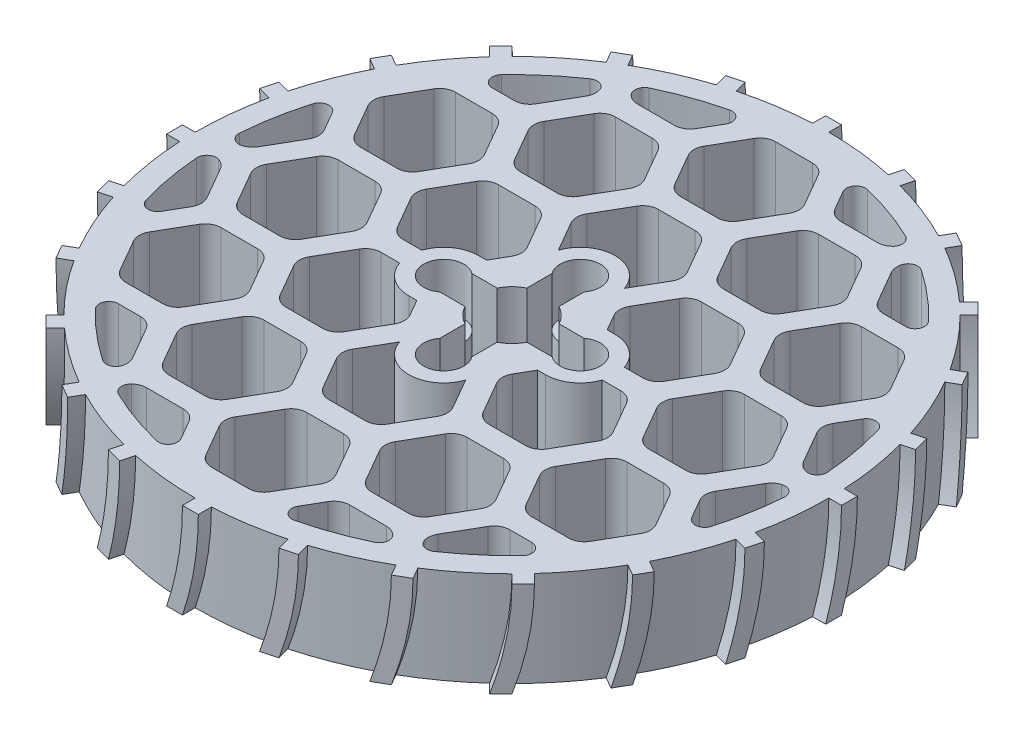
SolidWorks part; units mm, degrees
ref_plane "Front Plane" through (0, 0, 0) normal (0, 0, 1) x (1, 0, 0)
ref_plane "Top Plane" through (0, 0, 0) normal (0, 1, 0) x (1, 0, 0)
ref_plane "Right Plane" through (0, 0, 0) normal (1, 0, 0) x (0, 0, -1)
sketch "Sketch2" plane through (0, 0, 0) normal (0, 1, 0) x (1, 0, 0)
  line L0 (-17.7275, -5.0583) -> (-9.768, -5.0583)
  line L1 (-17.7275, 5.0583) -> (-9.768, 5.0583)
  line L2 (-21.548, 11) -> (-11, 11)
  line L3 (-21.548, -11) -> (-11, -11)
  line L4 (-21.548, 0) -> (0, 0) construction
  line L5 (11, 21.548) -> (11, 11)
  line L6 (-11, 21.548) -> (-11, 11)
  line L7 (5.0583, 17.7275) -> (5.0583, 9.768)
  line L8 (-5.0583, 17.7275) -> (-5.0583, 9.768)
  line L9 (21.548, -11) -> (11, -11)
  line L10 (21.548, 11) -> (11, 11)
  line L11 (17.7275, -5.0583) -> (9.768, -5.0583)
  line L12 (17.7275, 5.0583) -> (9.768, 5.0583)
  line L13 (-11, -21.548) -> (-11, -11)
  line L14 (11, -21.548) -> (11, -11)
  line L15 (-5.0583, -17.7275) -> (-5.0583, -9.768)
  line L16 (5.0583, -17.7275) -> (5.0583, -9.768)
  line L17 (0, 0) -> (-12.9904, 7.5) construction
  line L18 (-15.8771, -2.5) -> (-10.1036, -12.5)
  line L19 (-5.7735, -15) -> (5.7735, -15)
  line L20 (10.1036, -12.5) -> (15.8771, -2.5)
  line L21 (15.8771, 2.5) -> (10.1036, 12.5)
  line L22 (5.7735, 15) -> (-5.7735, 15)
  line L23 (-10.1036, 12.5) -> (-15.8771, 2.5)
  arc A0 (-21.548, 11) -> (-21.548, -11) centre (-21.548, 0) ccw
  arc A1 (-5.0583, 9.768) -> (-9.768, 5.0583) centre (0, 0) ccw
  circle A2 centre (-21.548, 0) radius 3.302
  circle A3 centre (-21.548, 0) radius 6.339
  arc A4 (-5.0583, 9.768) -> (-9.768, 5.0583) centre (0, 0) ccw
  arc A5 (11, 21.548) -> (-11, 21.548) centre (0, 21.548) ccw
  circle A6 centre (0, 21.548) radius 6.339
  circle A7 centre (0, 21.548) radius 3.302
  arc A8 (21.548, -11) -> (21.548, 11) centre (21.548, 0) ccw
  circle A9 centre (21.548, 0) radius 6.339
  circle A10 centre (21.548, 0) radius 3.302
  arc A11 (-11, -21.548) -> (11, -21.548) centre (0, -21.548) ccw
  circle A12 centre (0, -21.548) radius 6.339
  circle A13 centre (0, -21.548) radius 3.302
  arc A14 (9.768, 5.0583) -> (5.0583, 9.768) centre (0, 0) ccw
  arc A15 (5.0583, -9.768) -> (9.768, -5.0583) centre (0, 0) ccw
  arc A16 (-9.768, -5.0583) -> (-5.0583, -9.768) centre (0, 0) ccw
  circle A17 centre (0, 0) radius 100
  circle A18 centre (0, 0) radius 15 construction
  arc A19 (10.1036, 12.5) -> (5.7735, 15) centre (5.7735, 10) ccw
  arc A20 (15.8771, -2.5) -> (15.8771, 2.5) centre (11.547, 0) ccw
  arc A21 (10.1036, -12.5) -> (5.7735, -15) centre (5.7735, -10) cw
  arc A22 (-10.1036, -12.5) -> (-5.7735, -15) centre (-5.7735, -10) ccw
  arc A23 (-15.8771, -2.5) -> (-15.8771, 2.5) centre (-11.547, 0) cw
  arc A24 (-10.1036, 12.5) -> (-5.7735, 15) centre (-5.7735, 10) cw
  point P59 (0, 0)
  dimension "D1" = 6.604
  dimension "D2" = 12.678
  dimension "D3" = 11
  dimension "D8" = 22
  dimension "D10" = 200
  dimension "D12" = 5
  dimension "D4" = 21.548
  dimension "D5" = 7.9595
  dimension "D6" = 10.548
  dimension "D7" = 10.548
  dimension "D11" = 30
  dimension "D13" = 30
  dimension "D9" = 4
sketch "Sketch3" plane through (0, 0, 0) normal (0, 1, 0) x (1, 0, 0)
  line L0 (0, 0) -> (16.547, 0) construction
  line L1 (5.7735, 15) -> (-5.7735, 15)
  line L2 (-10.1036, 12.5) -> (-15.8771, 2.5)
  line L3 (-15.8771, -2.5) -> (-10.1036, -12.5)
  line L4 (-5.7735, -15) -> (5.7735, -15)
  line L5 (10.1036, -12.5) -> (15.8771, -2.5)
  line L6 (15.8771, 2.5) -> (10.1036, 12.5)
  line L7 (37.8164, 33.5) -> (26.2694, 33.5)
  line L8 (21.9393, 31) -> (16.1658, 21)
  line L9 (16.1658, 16) -> (21.9393, 6)
  line L10 (26.2694, 3.5) -> (37.8164, 3.5)
  line L11 (42.1466, 6) -> (47.9201, 16)
  line L12 (47.9201, 21) -> (42.1466, 31)
  line L13 (69.8594, 52) -> (58.3124, 52)
  line L14 (53.9823, 49.5) -> (48.2087, 39.5)
  line L15 (48.2087, 34.5) -> (53.9823, 24.5)
  line L16 (58.3124, 22) -> (69.8594, 22)
  line L17 (74.1895, 24.5) -> (79.963, 34.5)
  line L18 (79.963, 39.5) -> (74.1895, 49.5)
  line L19 (101.9023, 70.5) -> (90.3553, 70.5)
  line L20 (86.0252, 68) -> (80.2517, 58)
  line L21 (80.2517, 53) -> (86.0252, 43)
  line L22 (90.3553, 40.5) -> (101.9023, 40.5)
  line L23 (106.2324, 43) -> (112.006, 53)
  line L24 (112.006, 58) -> (106.2324, 68)
  line L25 (37.8164, 70.5) -> (26.2694, 70.5)
  line L26 (21.9393, 68) -> (16.1658, 58)
  line L27 (16.1658, 53) -> (21.9393, 43)
  line L28 (26.2694, 40.5) -> (37.8164, 40.5)
  line L29 (42.1466, 43) -> (47.9201, 53)
  line L30 (47.9201, 58) -> (42.1466, 68)
  line L31 (69.8594, 89) -> (58.3124, 89)
  line L32 (53.9823, 86.5) -> (48.2087, 76.5)
  line L33 (48.2087, 71.5) -> (53.9823, 61.5)
  line L34 (58.3124, 59) -> (69.8594, 59)
  line L35 (74.1895, 61.5) -> (79.963, 71.5)
  line L36 (79.963, 76.5) -> (74.1895, 86.5)
  line L37 (101.9023, 107.5) -> (90.3553, 107.5) [skipped]
  line L38 (86.0252, 105) -> (80.2517, 95) [skipped]
  line L39 (80.2517, 90) -> (86.0252, 80) [skipped]
  line L40 (90.3553, 77.5) -> (101.9023, 77.5) [skipped]
  line L41 (106.2324, 80) -> (112.006, 90) [skipped]
  line L42 (112.006, 95) -> (106.2324, 105) [skipped]
  line L43 (37.8164, 107.5) -> (26.2694, 107.5)
  line L44 (21.9393, 105) -> (16.1658, 95)
  line L45 (16.1658, 90) -> (21.9393, 80)
  line L46 (26.2694, 77.5) -> (37.8164, 77.5)
  line L47 (42.1466, 80) -> (47.9201, 90)
  line L48 (47.9201, 95) -> (42.1466, 105)
  line L49 (69.8594, 126) -> (58.3124, 126) [skipped]
  line L50 (53.9823, 123.5) -> (48.2087, 113.5) [skipped]
  line L51 (48.2087, 108.5) -> (53.9823, 98.5) [skipped]
  line L52 (58.3124, 96) -> (69.8594, 96) [skipped]
  line L53 (74.1895, 98.5) -> (79.963, 108.5) [skipped]
  line L54 (79.963, 113.5) -> (74.1895, 123.5) [skipped]
  line L55 (101.9023, 144.5) -> (90.3553, 144.5) [skipped]
  line L56 (86.0252, 142) -> (80.2517, 132) [skipped]
  line L57 (80.2517, 127) -> (86.0252, 117) [skipped]
  line L58 (90.3553, 114.5) -> (101.9023, 114.5) [skipped]
  line L59 (106.2324, 117) -> (112.006, 127) [skipped]
  line L60 (112.006, 132) -> (106.2324, 142) [skipped]
  line L61 (37.8164, 144.5) -> (26.2694, 144.5) [skipped]
  line L62 (21.9393, 142) -> (16.1658, 132) [skipped]
  line L63 (16.1658, 127) -> (21.9393, 117) [skipped]
  line L64 (26.2694, 114.5) -> (37.8164, 114.5) [skipped]
  line L65 (42.1466, 117) -> (47.9201, 127) [skipped]
  line L66 (47.9201, 132) -> (42.1466, 142) [skipped]
  line L67 (69.8594, 163) -> (58.3124, 163) [skipped]
  line L68 (53.9823, 160.5) -> (48.2087, 150.5) [skipped]
  line L69 (48.2087, 145.5) -> (53.9823, 135.5) [skipped]
  line L70 (58.3124, 133) -> (69.8594, 133) [skipped]
  line L71 (74.1895, 135.5) -> (79.963, 145.5) [skipped]
  line L72 (79.963, 150.5) -> (74.1895, 160.5) [skipped]
  line L73 (101.9023, 181.5) -> (90.3553, 181.5) [skipped]
  line L74 (86.0252, 179) -> (80.2517, 169) [skipped]
  line L75 (80.2517, 164) -> (86.0252, 154) [skipped]
  line L76 (90.3553, 151.5) -> (101.9023, 151.5) [skipped]
  line L77 (106.2324, 154) -> (112.006, 164) [skipped]
  line L78 (112.006, 169) -> (106.2324, 179) [skipped]
  line L79 (5.7735, 52) -> (-5.7735, 52) [skipped]
  line L80 (-10.1036, 49.5) -> (-15.8771, 39.5) [skipped]
  line L81 (-15.8771, 34.5) -> (-10.1036, 24.5) [skipped]
  line L82 (-5.7735, 22) -> (5.7735, 22) [skipped]
  line L83 (10.1036, 24.5) -> (15.8771, 34.5) [skipped]
  line L84 (15.8771, 39.5) -> (10.1036, 49.5) [skipped]
  line L85 (5.7735, 89) -> (-5.7735, 89) [skipped]
  line L86 (-10.1036, 86.5) -> (-15.8771, 76.5) [skipped]
  line L87 (-15.8771, 71.5) -> (-10.1036, 61.5) [skipped]
  line L88 (-5.7735, 59) -> (5.7735, 59) [skipped]
  line L89 (10.1036, 61.5) -> (15.8771, 71.5) [skipped]
  line L90 (15.8771, 76.5) -> (10.1036, 86.5) [skipped]
  line L91 (5.7735, 126) -> (-5.7735, 126) [skipped]
  line L92 (-10.1036, 123.5) -> (-15.8771, 113.5) [skipped]
  line L93 (-15.8771, 108.5) -> (-10.1036, 98.5) [skipped]
  line L94 (-5.7735, 96) -> (5.7735, 96) [skipped]
  line L95 (10.1036, 98.5) -> (15.8771, 108.5) [skipped]
  line L96 (15.8771, 113.5) -> (10.1036, 123.5) [skipped]
  line L97 (0, 0) -> (83.1384, 48) construction
  line L98 (112.006, 21) -> (106.2324, 31)
  line L99 (101.9023, 33.5) -> (90.3553, 33.5)
  line L100 (86.0252, 31) -> (80.2517, 21)
  line L101 (80.2517, 16) -> (86.0252, 6)
  line L102 (90.3553, 3.5) -> (101.9023, 3.5)
  line L103 (106.2324, 6) -> (112.006, 16)
  line L104 (112.006, -16) -> (106.2324, -6)
  line L105 (101.9023, -3.5) -> (90.3553, -3.5)
  line L106 (86.0252, -6) -> (80.2517, -16)
  line L107 (80.2517, -21) -> (86.0252, -31)
  line L108 (90.3553, -33.5) -> (101.9023, -33.5)
  line L109 (106.2324, -31) -> (112.006, -21)
  line L110 (112.006, -53) -> (106.2324, -43)
  line L111 (101.9023, -40.5) -> (90.3553, -40.5)
  line L112 (86.0252, -43) -> (80.2517, -53)
  line L113 (80.2517, -58) -> (86.0252, -68)
  line L114 (90.3553, -70.5) -> (101.9023, -70.5)
  line L115 (106.2324, -68) -> (112.006, -58)
  line L116 (79.963, -34.5) -> (74.1895, -24.5)
  line L117 (69.8594, -22) -> (58.3124, -22)
  line L118 (53.9823, -24.5) -> (48.2087, -34.5)
  line L119 (48.2087, -39.5) -> (53.9823, -49.5)
  line L120 (58.3124, -52) -> (69.8594, -52)
  line L121 (74.1895, -49.5) -> (79.963, -39.5)
  line L122 (79.963, 2.5) -> (74.1895, 12.5)
  line L123 (69.8594, 15) -> (58.3124, 15)
  line L124 (53.9823, 12.5) -> (48.2087, 2.5)
  line L125 (48.2087, -2.5) -> (53.9823, -12.5)
  line L126 (58.3124, -15) -> (69.8594, -15)
  line L127 (74.1895, -12.5) -> (79.963, -2.5)
  line L128 (47.9201, -16) -> (42.1466, -6)
  line L129 (37.8164, -3.5) -> (26.2694, -3.5)
  line L130 (21.9393, -6) -> (16.1658, -16)
  line L131 (16.1658, -21) -> (21.9393, -31)
  line L132 (26.2694, -33.5) -> (37.8164, -33.5)
  line L133 (42.1466, -31) -> (47.9201, -21)
  line L134 (74.1895, -86.5) -> (79.963, -76.5)
  line L135 (79.963, -71.5) -> (74.1895, -61.5)
  line L136 (69.8594, -59) -> (58.3124, -59)
  line L137 (53.9823, -61.5) -> (48.2087, -71.5)
  line L138 (48.2087, -76.5) -> (53.9823, -86.5)
  line L139 (58.3124, -89) -> (69.8594, -89)
  line L140 (42.1466, -105) -> (47.9201, -95)
  line L141 (47.9201, -90) -> (42.1466, -80)
  line L142 (37.8164, -77.5) -> (26.2694, -77.5)
  line L143 (21.9393, -80) -> (16.1658, -90)
  line L144 (16.1658, -95) -> (21.9393, -105)
  line L145 (26.2694, -107.5) -> (37.8164, -107.5)
  line L146 (10.1036, -123.5) -> (15.8771, -113.5)
  line L147 (15.8771, -108.5) -> (10.1036, -98.5)
  line L148 (5.7735, -96) -> (-5.7735, -96)
  line L149 (-10.1036, -98.5) -> (-15.8771, -108.5)
  line L150 (-15.8771, -113.5) -> (-10.1036, -123.5)
  line L151 (-5.7735, -126) -> (5.7735, -126)
  line L152 (10.1036, -86.5) -> (15.8771, -76.5)
  line L153 (15.8771, -71.5) -> (10.1036, -61.5)
  line L154 (5.7735, -59) -> (-5.7735, -59)
  line L155 (-10.1036, -61.5) -> (-15.8771, -71.5)
  line L156 (-15.8771, -76.5) -> (-10.1036, -86.5)
  line L157 (-5.7735, -89) -> (5.7735, -89)
  line L158 (42.1466, -68) -> (47.9201, -58)
  line L159 (47.9201, -53) -> (42.1466, -43)
  line L160 (37.8164, -40.5) -> (26.2694, -40.5)
  line L161 (21.9393, -43) -> (16.1658, -53)
  line L162 (16.1658, -58) -> (21.9393, -68)
  line L163 (26.2694, -70.5) -> (37.8164, -70.5)
  line L164 (10.1036, -49.5) -> (15.8771, -39.5)
  line L165 (15.8771, -34.5) -> (10.1036, -24.5)
  line L166 (5.7735, -22) -> (-5.7735, -22)
  line L167 (-10.1036, -24.5) -> (-15.8771, -34.5)
  line L168 (-15.8771, -39.5) -> (-10.1036, -49.5)
  line L169 (-5.7735, -52) -> (5.7735, -52)
  line L170 (-37.8164, -107.5) -> (-26.2694, -107.5)
  line L171 (-21.9393, -105) -> (-16.1658, -95)
  line L172 (-16.1658, -90) -> (-21.9393, -80)
  line L173 (-26.2694, -77.5) -> (-37.8164, -77.5)
  line L174 (-42.1466, -80) -> (-47.9201, -90)
  line L175 (-47.9201, -95) -> (-42.1466, -105)
  line L176 (-69.8594, -89) -> (-58.3124, -89)
  line L177 (-53.9823, -86.5) -> (-48.2087, -76.5)
  line L178 (-48.2087, -71.5) -> (-53.9823, -61.5)
  line L179 (-58.3124, -59) -> (-69.8594, -59)
  line L180 (-74.1895, -61.5) -> (-79.963, -71.5)
  line L181 (-79.963, -76.5) -> (-74.1895, -86.5)
  line L182 (-101.9023, -70.5) -> (-90.3553, -70.5)
  line L183 (-86.0252, -68) -> (-80.2517, -58)
  line L184 (-80.2517, -53) -> (-86.0252, -43)
  line L185 (-90.3553, -40.5) -> (-101.9023, -40.5)
  line L186 (-106.2324, -43) -> (-112.006, -53)
  line L187 (-112.006, -58) -> (-106.2324, -68)
  line L188 (-69.8594, -52) -> (-58.3124, -52)
  line L189 (-53.9823, -49.5) -> (-48.2087, -39.5)
  line L190 (-48.2087, -34.5) -> (-53.9823, -24.5)
  line L191 (-58.3124, -22) -> (-69.8594, -22)
  line L192 (-74.1895, -24.5) -> (-79.963, -34.5)
  line L193 (-79.963, -39.5) -> (-74.1895, -49.5)
  line L194 (-37.8164, -70.5) -> (-26.2694, -70.5)
  line L195 (-21.9393, -68) -> (-16.1658, -58)
  line L196 (-16.1658, -53) -> (-21.9393, -43)
  line L197 (-26.2694, -40.5) -> (-37.8164, -40.5)
  line L198 (-42.1466, -43) -> (-47.9201, -53)
  line L199 (-47.9201, -58) -> (-42.1466, -68)
  line L200 (-37.8164, -33.5) -> (-26.2694, -33.5)
  line L201 (-21.9393, -31) -> (-16.1658, -21)
  line L202 (-16.1658, -16) -> (-21.9393, -6)
  line L203 (-26.2694, -3.5) -> (-37.8164, -3.5)
  line L204 (-42.1466, -6) -> (-47.9201, -16)
  line L205 (-47.9201, -21) -> (-42.1466, -31)
  line L206 (-112.006, -21) -> (-106.2324, -31)
  line L207 (-101.9023, -33.5) -> (-90.3553, -33.5)
  line L208 (-86.0252, -31) -> (-80.2517, -21)
  line L209 (-80.2517, -16) -> (-86.0252, -6)
  line L210 (-90.3553, -3.5) -> (-101.9023, -3.5)
  line L211 (-106.2324, -6) -> (-112.006, -16)
  line L212 (-112.006, 16) -> (-106.2324, 6)
  line L213 (-101.9023, 3.5) -> (-90.3553, 3.5)
  line L214 (-86.0252, 6) -> (-80.2517, 16)
  line L215 (-80.2517, 21) -> (-86.0252, 31)
  line L216 (-90.3553, 33.5) -> (-101.9023, 33.5)
  line L217 (-106.2324, 31) -> (-112.006, 21)
  line L218 (-112.006, 53) -> (-106.2324, 43)
  line L219 (-101.9023, 40.5) -> (-90.3553, 40.5)
  line L220 (-86.0252, 43) -> (-80.2517, 53)
  line L221 (-80.2517, 58) -> (-86.0252, 68)
  line L222 (-90.3553, 70.5) -> (-101.9023, 70.5)
  line L223 (-106.2324, 68) -> (-112.006, 58)
  line L224 (-79.963, 34.5) -> (-74.1895, 24.5)
  line L225 (-69.8594, 22) -> (-58.3124, 22)
  line L226 (-53.9823, 24.5) -> (-48.2087, 34.5)
  line L227 (-48.2087, 39.5) -> (-53.9823, 49.5)
  line L228 (-58.3124, 52) -> (-69.8594, 52)
  line L229 (-74.1895, 49.5) -> (-79.963, 39.5)
  line L230 (-79.963, -2.5) -> (-74.1895, -12.5)
  line L231 (-69.8594, -15) -> (-58.3124, -15)
  line L232 (-53.9823, -12.5) -> (-48.2087, -2.5)
  line L233 (-48.2087, 2.5) -> (-53.9823, 12.5)
  line L234 (-58.3124, 15) -> (-69.8594, 15)
  line L235 (-74.1895, 12.5) -> (-79.963, 2.5)
  line L236 (-47.9201, 16) -> (-42.1466, 6)
  line L237 (-37.8164, 3.5) -> (-26.2694, 3.5)
  line L238 (-21.9393, 6) -> (-16.1658, 16)
  line L239 (-16.1658, 21) -> (-21.9393, 31)
  line L240 (-26.2694, 33.5) -> (-37.8164, 33.5)
  line L241 (-42.1466, 31) -> (-47.9201, 21)
  line L242 (-74.1895, 86.5) -> (-79.963, 76.5)
  line L243 (-79.963, 71.5) -> (-74.1895, 61.5)
  line L244 (-69.8594, 59) -> (-58.3124, 59)
  line L245 (-53.9823, 61.5) -> (-48.2087, 71.5)
  line L246 (-48.2087, 76.5) -> (-53.9823, 86.5)
  line L247 (-58.3124, 89) -> (-69.8594, 89)
  line L248 (-42.1466, 105) -> (-47.9201, 95)
  line L249 (-47.9201, 90) -> (-42.1466, 80)
  line L250 (-37.8164, 77.5) -> (-26.2694, 77.5)
  line L251 (-21.9393, 80) -> (-16.1658, 90)
  line L252 (-16.1658, 95) -> (-21.9393, 105)
  line L253 (-26.2694, 107.5) -> (-37.8164, 107.5)
  line L254 (-10.1036, 123.5) -> (-15.8771, 113.5)
  line L255 (-15.8771, 108.5) -> (-10.1036, 98.5)
  line L256 (-5.7735, 96) -> (5.7735, 96)
  line L257 (10.1036, 98.5) -> (15.8771, 108.5)
  line L258 (15.8771, 113.5) -> (10.1036, 123.5)
  line L259 (5.7735, 126) -> (-5.7735, 126)
  line L260 (-10.1036, 86.5) -> (-15.8771, 76.5)
  line L261 (-15.8771, 71.5) -> (-10.1036, 61.5)
  line L262 (-5.7735, 59) -> (5.7735, 59)
  line L263 (10.1036, 61.5) -> (15.8771, 71.5)
  line L264 (15.8771, 76.5) -> (10.1036, 86.5)
  line L265 (5.7735, 89) -> (-5.7735, 89)
  line L266 (-42.1466, 68) -> (-47.9201, 58)
  line L267 (-47.9201, 53) -> (-42.1466, 43)
  line L268 (-37.8164, 40.5) -> (-26.2694, 40.5)
  line L269 (-21.9393, 43) -> (-16.1658, 53)
  line L270 (-16.1658, 58) -> (-21.9393, 68)
  line L271 (-26.2694, 70.5) -> (-37.8164, 70.5)
  line L272 (-10.1036, 49.5) -> (-15.8771, 39.5)
  line L273 (-15.8771, 34.5) -> (-10.1036, 24.5)
  line L274 (-5.7735, 22) -> (5.7735, 22)
  line L275 (10.1036, 24.5) -> (15.8771, 34.5)
  line L276 (15.8771, 39.5) -> (10.1036, 49.5)
  line L277 (5.7735, 52) -> (-5.7735, 52)
  line L278 (0, 0) -> (0, 96) construction
  line L279 (0, 0) -> (-83.1384, 48) construction
  line L280 (-17.7275, -5.0583) -> (-9.768, -5.0583)
  line L281 (-17.7275, 5.0583) -> (-9.768, 5.0583)
  line L282 (-21.548, 11) -> (-11, 11)
  line L283 (-21.548, -11) -> (-11, -11)
  line L284 (0, 0) -> (-21.548, 0) construction
  line L285 (11, 21.548) -> (11, 11)
  line L286 (-11, 21.548) -> (-11, 11)
  line L287 (-5.0583, 17.7275) -> (-5.0583, 9.768)
  line L288 (5.0583, 17.7275) -> (5.0583, 9.768)
  line L289 (21.548, -11) -> (11, -11)
  line L290 (21.548, 11) -> (11, 11)
  line L291 (17.7275, 5.0583) -> (9.768, 5.0583)
  line L292 (17.7275, -5.0583) -> (9.768, -5.0583)
  line L293 (-11, -21.548) -> (-11, -11)
  line L294 (11, -21.548) -> (11, -11)
  line L295 (5.0583, -17.7275) -> (5.0583, -9.768)
  line L296 (-5.0583, -17.7275) -> (-5.0583, -9.768)
  line L297 (0, 0) -> (0, 21.548) construction
  circle A0 centre (0, 0) radius 15 construction
  arc A1 (10.1036, 12.5) -> (5.7735, 15) centre (5.7735, 10) ccw
  arc A2 (15.8771, 2.5) -> (15.8771, -2.5) centre (11.547, 0) cw
  arc A3 (5.7735, -15) -> (10.1036, -12.5) centre (5.7735, -10) ccw
  arc A4 (-5.7735, -15) -> (-10.1036, -12.5) centre (-5.7735, -10) cw
  arc A5 (-15.8771, -2.5) -> (-15.8771, 2.5) centre (-11.547, 0) cw
  arc A6 (-10.1036, 12.5) -> (-5.7735, 15) centre (-5.7735, 10) cw
  circle A7 centre (0, 0) radius 100
  arc A8 (21.9393, 31) -> (26.2694, 33.5) centre (26.2694, 28.5) cw
  arc A9 (42.1466, 31) -> (37.8164, 33.5) centre (37.8164, 28.5) ccw
  arc A10 (16.1658, 16) -> (16.1658, 21) centre (20.4959, 18.5) cw
  arc A11 (26.2694, 3.5) -> (21.9393, 6) centre (26.2694, 8.5) cw
  arc A12 (37.8164, 3.5) -> (42.1466, 6) centre (37.8164, 8.5) ccw
  arc A13 (47.9201, 21) -> (47.9201, 16) centre (43.5899, 18.5) cw
  arc A14 (53.9823, 49.5) -> (58.3124, 52) centre (58.3124, 47) cw
  arc A15 (74.1895, 49.5) -> (69.8594, 52) centre (69.8594, 47) ccw
  arc A16 (48.2087, 34.5) -> (48.2087, 39.5) centre (52.5389, 37) cw
  arc A17 (58.3124, 22) -> (53.9823, 24.5) centre (58.3124, 27) cw
  arc A18 (69.8594, 22) -> (74.1895, 24.5) centre (69.8594, 27) ccw
  arc A19 (79.963, 39.5) -> (79.963, 34.5) centre (75.6329, 37) cw
  arc A20 (86.0252, 68) -> (90.3553, 70.5) centre (90.3553, 65.5) cw
  arc A21 (106.2324, 68) -> (101.9023, 70.5) centre (101.9023, 65.5) ccw
  arc A22 (80.2517, 53) -> (80.2517, 58) centre (84.5818, 55.5) cw
  arc A23 (90.3553, 40.5) -> (86.0252, 43) centre (90.3553, 45.5) cw
  arc A24 (101.9023, 40.5) -> (106.2324, 43) centre (101.9023, 45.5) ccw
  arc A25 (112.006, 58) -> (112.006, 53) centre (107.6758, 55.5) cw
  arc A26 (21.9393, 68) -> (26.2694, 70.5) centre (26.2694, 65.5) cw
  arc A27 (42.1466, 68) -> (37.8164, 70.5) centre (37.8164, 65.5) ccw
  arc A28 (16.1658, 53) -> (16.1658, 58) centre (20.4959, 55.5) cw
  arc A29 (26.2694, 40.5) -> (21.9393, 43) centre (26.2694, 45.5) cw
  arc A30 (37.8164, 40.5) -> (42.1466, 43) centre (37.8164, 45.5) ccw
  arc A31 (47.9201, 58) -> (47.9201, 53) centre (43.5899, 55.5) cw
  arc A32 (53.9823, 86.5) -> (58.3124, 89) centre (58.3124, 84) cw
  arc A33 (74.1895, 86.5) -> (69.8594, 89) centre (69.8594, 84) ccw
  arc A34 (48.2087, 71.5) -> (48.2087, 76.5) centre (52.5389, 74) cw
  arc A35 (58.3124, 59) -> (53.9823, 61.5) centre (58.3124, 64) cw
  arc A36 (69.8594, 59) -> (74.1895, 61.5) centre (69.8594, 64) ccw
  arc A37 (79.963, 76.5) -> (79.963, 71.5) centre (75.6329, 74) cw
  arc A38 (86.0252, 105) -> (90.3553, 107.5) centre (90.3553, 102.5) cw [skipped]
  arc A39 (106.2324, 105) -> (101.9023, 107.5) centre (101.9023, 102.5) ccw [skipped]
  arc A40 (80.2517, 90) -> (80.2517, 95) centre (84.5818, 92.5) cw [skipped]
  arc A41 (90.3553, 77.5) -> (86.0252, 80) centre (90.3553, 82.5) cw [skipped]
  arc A42 (101.9023, 77.5) -> (106.2324, 80) centre (101.9023, 82.5) ccw [skipped]
  arc A43 (112.006, 95) -> (112.006, 90) centre (107.6758, 92.5) cw [skipped]
  arc A44 (21.9393, 105) -> (26.2694, 107.5) centre (26.2694, 102.5) cw
  arc A45 (42.1466, 105) -> (37.8164, 107.5) centre (37.8164, 102.5) ccw
  arc A46 (16.1658, 90) -> (16.1658, 95) centre (20.4959, 92.5) cw
  arc A47 (26.2694, 77.5) -> (21.9393, 80) centre (26.2694, 82.5) cw
  arc A48 (37.8164, 77.5) -> (42.1466, 80) centre (37.8164, 82.5) ccw
  arc A49 (47.9201, 95) -> (47.9201, 90) centre (43.5899, 92.5) cw
  arc A50 (53.9823, 123.5) -> (58.3124, 126) centre (58.3124, 121) cw [skipped]
  arc A51 (74.1895, 123.5) -> (69.8594, 126) centre (69.8594, 121) ccw [skipped]
  arc A52 (48.2087, 108.5) -> (48.2087, 113.5) centre (52.5389, 111) cw [skipped]
  arc A53 (58.3124, 96) -> (53.9823, 98.5) centre (58.3124, 101) cw [skipped]
  arc A54 (69.8594, 96) -> (74.1895, 98.5) centre (69.8594, 101) ccw [skipped]
  arc A55 (79.963, 113.5) -> (79.963, 108.5) centre (75.6329, 111) cw [skipped]
  arc A56 (86.0252, 142) -> (90.3553, 144.5) centre (90.3553, 139.5) cw [skipped]
  arc A57 (106.2324, 142) -> (101.9023, 144.5) centre (101.9023, 139.5) ccw [skipped]
  arc A58 (80.2517, 127) -> (80.2517, 132) centre (84.5818, 129.5) cw [skipped]
  arc A59 (90.3553, 114.5) -> (86.0252, 117) centre (90.3553, 119.5) cw [skipped]
  arc A60 (101.9023, 114.5) -> (106.2324, 117) centre (101.9023, 119.5) ccw [skipped]
  arc A61 (112.006, 132) -> (112.006, 127) centre (107.6758, 129.5) cw [skipped]
  arc A62 (21.9393, 142) -> (26.2694, 144.5) centre (26.2694, 139.5) cw [skipped]
  arc A63 (42.1466, 142) -> (37.8164, 144.5) centre (37.8164, 139.5) ccw [skipped]
  arc A64 (16.1658, 127) -> (16.1658, 132) centre (20.4959, 129.5) cw [skipped]
  arc A65 (26.2694, 114.5) -> (21.9393, 117) centre (26.2694, 119.5) cw [skipped]
  arc A66 (37.8164, 114.5) -> (42.1466, 117) centre (37.8164, 119.5) ccw [skipped]
  arc A67 (47.9201, 132) -> (47.9201, 127) centre (43.5899, 129.5) cw [skipped]
  arc A68 (53.9823, 160.5) -> (58.3124, 163) centre (58.3124, 158) cw [skipped]
  arc A69 (74.1895, 160.5) -> (69.8594, 163) centre (69.8594, 158) ccw [skipped]
  arc A70 (48.2087, 145.5) -> (48.2087, 150.5) centre (52.5389, 148) cw [skipped]
  arc A71 (58.3124, 133) -> (53.9823, 135.5) centre (58.3124, 138) cw [skipped]
  arc A72 (69.8594, 133) -> (74.1895, 135.5) centre (69.8594, 138) ccw [skipped]
  arc A73 (79.963, 150.5) -> (79.963, 145.5) centre (75.6329, 148) cw [skipped]
  arc A74 (86.0252, 179) -> (90.3553, 181.5) centre (90.3553, 176.5) cw [skipped]
  arc A75 (106.2324, 179) -> (101.9023, 181.5) centre (101.9023, 176.5) ccw [skipped]
  arc A76 (80.2517, 164) -> (80.2517, 169) centre (84.5818, 166.5) cw [skipped]
  arc A77 (90.3553, 151.5) -> (86.0252, 154) centre (90.3553, 156.5) cw [skipped]
  arc A78 (101.9023, 151.5) -> (106.2324, 154) centre (101.9023, 156.5) ccw [skipped]
  arc A79 (112.006, 169) -> (112.006, 164) centre (107.6758, 166.5) cw [skipped]
  arc A80 (-10.1036, 49.5) -> (-5.7735, 52) centre (-5.7735, 47) cw [skipped]
  arc A81 (10.1036, 49.5) -> (5.7735, 52) centre (5.7735, 47) ccw [skipped]
  arc A82 (-15.8771, 34.5) -> (-15.8771, 39.5) centre (-11.547, 37) cw [skipped]
  arc A83 (-5.7735, 22) -> (-10.1036, 24.5) centre (-5.7735, 27) cw [skipped]
  arc A84 (5.7735, 22) -> (10.1036, 24.5) centre (5.7735, 27) ccw [skipped]
  arc A85 (15.8771, 39.5) -> (15.8771, 34.5) centre (11.547, 37) cw [skipped]
  arc A86 (-10.1036, 86.5) -> (-5.7735, 89) centre (-5.7735, 84) cw [skipped]
  arc A87 (10.1036, 86.5) -> (5.7735, 89) centre (5.7735, 84) ccw [skipped]
  arc A88 (-15.8771, 71.5) -> (-15.8771, 76.5) centre (-11.547, 74) cw [skipped]
  arc A89 (-5.7735, 59) -> (-10.1036, 61.5) centre (-5.7735, 64) cw [skipped]
  arc A90 (5.7735, 59) -> (10.1036, 61.5) centre (5.7735, 64) ccw [skipped]
  arc A91 (15.8771, 76.5) -> (15.8771, 71.5) centre (11.547, 74) cw [skipped]
  arc A92 (-10.1036, 123.5) -> (-5.7735, 126) centre (-5.7735, 121) cw [skipped]
  arc A93 (10.1036, 123.5) -> (5.7735, 126) centre (5.7735, 121) ccw [skipped]
  arc A94 (-15.8771, 108.5) -> (-15.8771, 113.5) centre (-11.547, 111) cw [skipped]
  arc A95 (-5.7735, 96) -> (-10.1036, 98.5) centre (-5.7735, 101) cw [skipped]
  arc A96 (5.7735, 96) -> (10.1036, 98.5) centre (5.7735, 101) ccw [skipped]
  arc A97 (15.8771, 113.5) -> (15.8771, 108.5) centre (11.547, 111) cw [skipped]
  arc A98 (101.9023, 33.5) -> (106.2324, 31) centre (101.9023, 28.5) cw
  arc A99 (86.0252, 31) -> (90.3553, 33.5) centre (90.3553, 28.5) cw
  arc A100 (80.2517, 16) -> (80.2517, 21) centre (84.5818, 18.5) cw
  arc A101 (86.0252, 6) -> (90.3553, 3.5) centre (90.3553, 8.5) ccw
  arc A102 (106.2324, 6) -> (101.9023, 3.5) centre (101.9023, 8.5) cw
  arc A103 (112.006, 16) -> (112.006, 21) centre (107.6758, 18.5) ccw
  arc A104 (101.9023, -3.5) -> (106.2324, -6) centre (101.9023, -8.5) cw
  arc A105 (86.0252, -6) -> (90.3553, -3.5) centre (90.3553, -8.5) cw
  arc A106 (80.2517, -21) -> (80.2517, -16) centre (84.5818, -18.5) cw
  arc A107 (86.0252, -31) -> (90.3553, -33.5) centre (90.3553, -28.5) ccw
  arc A108 (106.2324, -31) -> (101.9023, -33.5) centre (101.9023, -28.5) cw
  arc A109 (112.006, -21) -> (112.006, -16) centre (107.6758, -18.5) ccw
  arc A110 (101.9023, -40.5) -> (106.2324, -43) centre (101.9023, -45.5) cw
  arc A111 (86.0252, -43) -> (90.3553, -40.5) centre (90.3553, -45.5) cw
  arc A112 (80.2517, -58) -> (80.2517, -53) centre (84.5818, -55.5) cw
  arc A113 (86.0252, -68) -> (90.3553, -70.5) centre (90.3553, -65.5) ccw
  arc A114 (106.2324, -68) -> (101.9023, -70.5) centre (101.9023, -65.5) cw
  arc A115 (112.006, -58) -> (112.006, -53) centre (107.6758, -55.5) ccw
  arc A116 (69.8594, -22) -> (74.1895, -24.5) centre (69.8594, -27) cw
  arc A117 (53.9823, -24.5) -> (58.3124, -22) centre (58.3124, -27) cw
  arc A118 (48.2087, -39.5) -> (48.2087, -34.5) centre (52.5389, -37) cw
  arc A119 (53.9823, -49.5) -> (58.3124, -52) centre (58.3124, -47) ccw
  arc A120 (74.1895, -49.5) -> (69.8594, -52) centre (69.8594, -47) cw
  arc A121 (79.963, -39.5) -> (79.963, -34.5) centre (75.6329, -37) ccw
  arc A122 (69.8594, 15) -> (74.1895, 12.5) centre (69.8594, 10) cw
  arc A123 (53.9823, 12.5) -> (58.3124, 15) centre (58.3124, 10) cw
  arc A124 (48.2087, -2.5) -> (48.2087, 2.5) centre (52.5389, 0) cw
  arc A125 (53.9823, -12.5) -> (58.3124, -15) centre (58.3124, -10) ccw
  arc A126 (74.1895, -12.5) -> (69.8594, -15) centre (69.8594, -10) cw
  arc A127 (79.963, -2.5) -> (79.963, 2.5) centre (75.6329, 0) ccw
  arc A128 (37.8164, -3.5) -> (42.1466, -6) centre (37.8164, -8.5) cw
  arc A129 (21.9393, -6) -> (26.2694, -3.5) centre (26.2694, -8.5) cw
  arc A130 (16.1658, -21) -> (16.1658, -16) centre (20.4959, -18.5) cw
  arc A131 (21.9393, -31) -> (26.2694, -33.5) centre (26.2694, -28.5) ccw
  arc A132 (42.1466, -31) -> (37.8164, -33.5) centre (37.8164, -28.5) cw
  arc A133 (47.9201, -21) -> (47.9201, -16) centre (43.5899, -18.5) ccw
  arc A134 (79.963, -71.5) -> (79.963, -76.5) centre (75.6329, -74) cw
  arc A135 (69.8594, -59) -> (74.1895, -61.5) centre (69.8594, -64) cw
  arc A136 (53.9823, -61.5) -> (58.3124, -59) centre (58.3124, -64) cw
  arc A137 (48.2087, -71.5) -> (48.2087, -76.5) centre (52.5389, -74) ccw
  arc A138 (58.3124, -89) -> (53.9823, -86.5) centre (58.3124, -84) cw
  arc A139 (69.8594, -89) -> (74.1895, -86.5) centre (69.8594, -84) ccw
  arc A140 (47.9201, -90) -> (47.9201, -95) centre (43.5899, -92.5) cw
  arc A141 (37.8164, -77.5) -> (42.1466, -80) centre (37.8164, -82.5) cw
  arc A142 (21.9393, -80) -> (26.2694, -77.5) centre (26.2694, -82.5) cw
  arc A143 (16.1658, -90) -> (16.1658, -95) centre (20.4959, -92.5) ccw
  arc A144 (26.2694, -107.5) -> (21.9393, -105) centre (26.2694, -102.5) cw
  arc A145 (37.8164, -107.5) -> (42.1466, -105) centre (37.8164, -102.5) ccw
  arc A146 (15.8771, -108.5) -> (15.8771, -113.5) centre (11.547, -111) cw
  arc A147 (5.7735, -96) -> (10.1036, -98.5) centre (5.7735, -101) cw
  arc A148 (-10.1036, -98.5) -> (-5.7735, -96) centre (-5.7735, -101) cw
  arc A149 (-15.8771, -108.5) -> (-15.8771, -113.5) centre (-11.547, -111) ccw
  arc A150 (-5.7735, -126) -> (-10.1036, -123.5) centre (-5.7735, -121) cw
  arc A151 (5.7735, -126) -> (10.1036, -123.5) centre (5.7735, -121) ccw
  arc A152 (15.8771, -71.5) -> (15.8771, -76.5) centre (11.547, -74) cw
  arc A153 (5.7735, -59) -> (10.1036, -61.5) centre (5.7735, -64) cw
  arc A154 (-10.1036, -61.5) -> (-5.7735, -59) centre (-5.7735, -64) cw
  arc A155 (-15.8771, -71.5) -> (-15.8771, -76.5) centre (-11.547, -74) ccw
  arc A156 (-5.7735, -89) -> (-10.1036, -86.5) centre (-5.7735, -84) cw
  arc A157 (5.7735, -89) -> (10.1036, -86.5) centre (5.7735, -84) ccw
  arc A158 (47.9201, -53) -> (47.9201, -58) centre (43.5899, -55.5) cw
  arc A159 (37.8164, -40.5) -> (42.1466, -43) centre (37.8164, -45.5) cw
  arc A160 (21.9393, -43) -> (26.2694, -40.5) centre (26.2694, -45.5) cw
  arc A161 (16.1658, -53) -> (16.1658, -58) centre (20.4959, -55.5) ccw
  arc A162 (26.2694, -70.5) -> (21.9393, -68) centre (26.2694, -65.5) cw
  arc A163 (37.8164, -70.5) -> (42.1466, -68) centre (37.8164, -65.5) ccw
  arc A164 (15.8771, -34.5) -> (15.8771, -39.5) centre (11.547, -37) cw
  arc A165 (5.7735, -22) -> (10.1036, -24.5) centre (5.7735, -27) cw
  arc A166 (-10.1036, -24.5) -> (-5.7735, -22) centre (-5.7735, -27) cw
  arc A167 (-15.8771, -34.5) -> (-15.8771, -39.5) centre (-11.547, -37) ccw
  arc A168 (-5.7735, -52) -> (-10.1036, -49.5) centre (-5.7735, -47) cw
  arc A169 (5.7735, -52) -> (10.1036, -49.5) centre (5.7735, -47) ccw
  arc A170 (-21.9393, -105) -> (-26.2694, -107.5) centre (-26.2694, -102.5) cw
  arc A171 (-16.1658, -90) -> (-16.1658, -95) centre (-20.4959, -92.5) cw
  arc A172 (-26.2694, -77.5) -> (-21.9393, -80) centre (-26.2694, -82.5) cw
  arc A173 (-37.8164, -77.5) -> (-42.1466, -80) centre (-37.8164, -82.5) ccw
  arc A174 (-47.9201, -95) -> (-47.9201, -90) centre (-43.5899, -92.5) cw
  arc A175 (-42.1466, -105) -> (-37.8164, -107.5) centre (-37.8164, -102.5) ccw
  arc A176 (-53.9823, -86.5) -> (-58.3124, -89) centre (-58.3124, -84) cw
  arc A177 (-48.2087, -71.5) -> (-48.2087, -76.5) centre (-52.5389, -74) cw
  arc A178 (-58.3124, -59) -> (-53.9823, -61.5) centre (-58.3124, -64) cw
  arc A179 (-69.8594, -59) -> (-74.1895, -61.5) centre (-69.8594, -64) ccw
  arc A180 (-79.963, -76.5) -> (-79.963, -71.5) centre (-75.6329, -74) cw
  arc A181 (-74.1895, -86.5) -> (-69.8594, -89) centre (-69.8594, -84) ccw
  arc A182 (-86.0252, -68) -> (-90.3553, -70.5) centre (-90.3553, -65.5) cw
  arc A183 (-80.2517, -53) -> (-80.2517, -58) centre (-84.5818, -55.5) cw
  arc A184 (-90.3553, -40.5) -> (-86.0252, -43) centre (-90.3553, -45.5) cw
  arc A185 (-101.9023, -40.5) -> (-106.2324, -43) centre (-101.9023, -45.5) ccw
  arc A186 (-112.006, -58) -> (-112.006, -53) centre (-107.6758, -55.5) cw
  arc A187 (-106.2324, -68) -> (-101.9023, -70.5) centre (-101.9023, -65.5) ccw
  arc A188 (-53.9823, -49.5) -> (-58.3124, -52) centre (-58.3124, -47) cw
  arc A189 (-48.2087, -34.5) -> (-48.2087, -39.5) centre (-52.5389, -37) cw
  arc A190 (-58.3124, -22) -> (-53.9823, -24.5) centre (-58.3124, -27) cw
  arc A191 (-69.8594, -22) -> (-74.1895, -24.5) centre (-69.8594, -27) ccw
  arc A192 (-79.963, -39.5) -> (-79.963, -34.5) centre (-75.6329, -37) cw
  arc A193 (-74.1895, -49.5) -> (-69.8594, -52) centre (-69.8594, -47) ccw
  arc A194 (-21.9393, -68) -> (-26.2694, -70.5) centre (-26.2694, -65.5) cw
  arc A195 (-16.1658, -53) -> (-16.1658, -58) centre (-20.4959, -55.5) cw
  arc A196 (-26.2694, -40.5) -> (-21.9393, -43) centre (-26.2694, -45.5) cw
  arc A197 (-37.8164, -40.5) -> (-42.1466, -43) centre (-37.8164, -45.5) ccw
  arc A198 (-47.9201, -58) -> (-47.9201, -53) centre (-43.5899, -55.5) cw
  arc A199 (-42.1466, -68) -> (-37.8164, -70.5) centre (-37.8164, -65.5) ccw
  arc A200 (-21.9393, -31) -> (-26.2694, -33.5) centre (-26.2694, -28.5) cw
  arc A201 (-16.1658, -16) -> (-16.1658, -21) centre (-20.4959, -18.5) cw
  arc A202 (-26.2694, -3.5) -> (-21.9393, -6) centre (-26.2694, -8.5) cw
  arc A203 (-37.8164, -3.5) -> (-42.1466, -6) centre (-37.8164, -8.5) ccw
  arc A204 (-47.9201, -21) -> (-47.9201, -16) centre (-43.5899, -18.5) cw
  arc A205 (-42.1466, -31) -> (-37.8164, -33.5) centre (-37.8164, -28.5) ccw
  arc A206 (-101.9023, -33.5) -> (-106.2324, -31) centre (-101.9023, -28.5) cw
  arc A207 (-86.0252, -31) -> (-90.3553, -33.5) centre (-90.3553, -28.5) cw
  arc A208 (-80.2517, -16) -> (-80.2517, -21) centre (-84.5818, -18.5) cw
  arc A209 (-86.0252, -6) -> (-90.3553, -3.5) centre (-90.3553, -8.5) ccw
  arc A210 (-106.2324, -6) -> (-101.9023, -3.5) centre (-101.9023, -8.5) cw
  arc A211 (-112.006, -16) -> (-112.006, -21) centre (-107.6758, -18.5) ccw
  arc A212 (-101.9023, 3.5) -> (-106.2324, 6) centre (-101.9023, 8.5) cw
  arc A213 (-86.0252, 6) -> (-90.3553, 3.5) centre (-90.3553, 8.5) cw
  arc A214 (-80.2517, 21) -> (-80.2517, 16) centre (-84.5818, 18.5) cw
  arc A215 (-86.0252, 31) -> (-90.3553, 33.5) centre (-90.3553, 28.5) ccw
  arc A216 (-106.2324, 31) -> (-101.9023, 33.5) centre (-101.9023, 28.5) cw
  arc A217 (-112.006, 21) -> (-112.006, 16) centre (-107.6758, 18.5) ccw
  arc A218 (-101.9023, 40.5) -> (-106.2324, 43) centre (-101.9023, 45.5) cw
  arc A219 (-86.0252, 43) -> (-90.3553, 40.5) centre (-90.3553, 45.5) cw
  arc A220 (-80.2517, 58) -> (-80.2517, 53) centre (-84.5818, 55.5) cw
  arc A221 (-86.0252, 68) -> (-90.3553, 70.5) centre (-90.3553, 65.5) ccw
  arc A222 (-106.2324, 68) -> (-101.9023, 70.5) centre (-101.9023, 65.5) cw
  arc A223 (-112.006, 58) -> (-112.006, 53) centre (-107.6758, 55.5) ccw
  arc A224 (-69.8594, 22) -> (-74.1895, 24.5) centre (-69.8594, 27) cw
  arc A225 (-53.9823, 24.5) -> (-58.3124, 22) centre (-58.3124, 27) cw
  arc A226 (-48.2087, 39.5) -> (-48.2087, 34.5) centre (-52.5389, 37) cw
  arc A227 (-53.9823, 49.5) -> (-58.3124, 52) centre (-58.3124, 47) ccw
  arc A228 (-74.1895, 49.5) -> (-69.8594, 52) centre (-69.8594, 47) cw
  arc A229 (-79.963, 39.5) -> (-79.963, 34.5) centre (-75.6329, 37) ccw
  arc A230 (-69.8594, -15) -> (-74.1895, -12.5) centre (-69.8594, -10) cw
  arc A231 (-53.9823, -12.5) -> (-58.3124, -15) centre (-58.3124, -10) cw
  arc A232 (-48.2087, 2.5) -> (-48.2087, -2.5) centre (-52.5389, 0) cw
  arc A233 (-53.9823, 12.5) -> (-58.3124, 15) centre (-58.3124, 10) ccw
  arc A234 (-74.1895, 12.5) -> (-69.8594, 15) centre (-69.8594, 10) cw
  arc A235 (-79.963, 2.5) -> (-79.963, -2.5) centre (-75.6329, 0) ccw
  arc A236 (-37.8164, 3.5) -> (-42.1466, 6) centre (-37.8164, 8.5) cw
  arc A237 (-21.9393, 6) -> (-26.2694, 3.5) centre (-26.2694, 8.5) cw
  arc A238 (-16.1658, 21) -> (-16.1658, 16) centre (-20.4959, 18.5) cw
  arc A239 (-21.9393, 31) -> (-26.2694, 33.5) centre (-26.2694, 28.5) ccw
  arc A240 (-42.1466, 31) -> (-37.8164, 33.5) centre (-37.8164, 28.5) cw
  arc A241 (-47.9201, 21) -> (-47.9201, 16) centre (-43.5899, 18.5) ccw
  arc A242 (-79.963, 71.5) -> (-79.963, 76.5) centre (-75.6329, 74) cw
  arc A243 (-69.8594, 59) -> (-74.1895, 61.5) centre (-69.8594, 64) cw
  arc A244 (-53.9823, 61.5) -> (-58.3124, 59) centre (-58.3124, 64) cw
  arc A245 (-48.2087, 71.5) -> (-48.2087, 76.5) centre (-52.5389, 74) ccw
  arc A246 (-58.3124, 89) -> (-53.9823, 86.5) centre (-58.3124, 84) cw
  arc A247 (-69.8594, 89) -> (-74.1895, 86.5) centre (-69.8594, 84) ccw
  arc A248 (-47.9201, 90) -> (-47.9201, 95) centre (-43.5899, 92.5) cw
  arc A249 (-37.8164, 77.5) -> (-42.1466, 80) centre (-37.8164, 82.5) cw
  arc A250 (-21.9393, 80) -> (-26.2694, 77.5) centre (-26.2694, 82.5) cw
  arc A251 (-16.1658, 90) -> (-16.1658, 95) centre (-20.4959, 92.5) ccw
  arc A252 (-26.2694, 107.5) -> (-21.9393, 105) centre (-26.2694, 102.5) cw
  arc A253 (-37.8164, 107.5) -> (-42.1466, 105) centre (-37.8164, 102.5) ccw
  arc A254 (-15.8771, 108.5) -> (-15.8771, 113.5) centre (-11.547, 111) cw
  arc A255 (-5.7735, 96) -> (-10.1036, 98.5) centre (-5.7735, 101) cw
  arc A256 (10.1036, 98.5) -> (5.7735, 96) centre (5.7735, 101) cw
  arc A257 (15.8771, 108.5) -> (15.8771, 113.5) centre (11.547, 111) ccw
  arc A258 (5.7735, 126) -> (10.1036, 123.5) centre (5.7735, 121) cw
  arc A259 (-5.7735, 126) -> (-10.1036, 123.5) centre (-5.7735, 121) ccw
  arc A260 (-15.8771, 71.5) -> (-15.8771, 76.5) centre (-11.547, 74) cw
  arc A261 (-5.7735, 59) -> (-10.1036, 61.5) centre (-5.7735, 64) cw
  arc A262 (10.1036, 61.5) -> (5.7735, 59) centre (5.7735, 64) cw
  arc A263 (15.8771, 71.5) -> (15.8771, 76.5) centre (11.547, 74) ccw
  arc A264 (5.7735, 89) -> (10.1036, 86.5) centre (5.7735, 84) cw
  arc A265 (-5.7735, 89) -> (-10.1036, 86.5) centre (-5.7735, 84) ccw
  arc A266 (-47.9201, 53) -> (-47.9201, 58) centre (-43.5899, 55.5) cw
  arc A267 (-37.8164, 40.5) -> (-42.1466, 43) centre (-37.8164, 45.5) cw
  arc A268 (-21.9393, 43) -> (-26.2694, 40.5) centre (-26.2694, 45.5) cw
  arc A269 (-16.1658, 53) -> (-16.1658, 58) centre (-20.4959, 55.5) ccw
  arc A270 (-26.2694, 70.5) -> (-21.9393, 68) centre (-26.2694, 65.5) cw
  arc A271 (-37.8164, 70.5) -> (-42.1466, 68) centre (-37.8164, 65.5) ccw
  arc A272 (-15.8771, 34.5) -> (-15.8771, 39.5) centre (-11.547, 37) cw
  arc A273 (-5.7735, 22) -> (-10.1036, 24.5) centre (-5.7735, 27) cw
  arc A274 (10.1036, 24.5) -> (5.7735, 22) centre (5.7735, 27) cw
  arc A275 (15.8771, 34.5) -> (15.8771, 39.5) centre (11.547, 37) ccw
  arc A276 (5.7735, 52) -> (10.1036, 49.5) centre (5.7735, 47) cw
  arc A277 (-5.7735, 52) -> (-10.1036, 49.5) centre (-5.7735, 47) ccw
  circle A278 centre (0, 0) radius 93
  arc A279 (-21.548, 11) -> (-21.548, -11) centre (-21.548, 0) ccw
  circle A280 centre (-21.548, 0) radius 3.302
  circle A281 centre (-21.548, 0) radius 6.339
  arc A282 (9.768, 5.0583) -> (9.768, -5.0583) centre (0, 0) ccw construction
  circle A283 centre (0, 0) radius 11
  arc A284 (11, 21.548) -> (-11, 21.548) centre (0, 21.548) ccw
  circle A285 centre (0, 21.548) radius 6.339
  circle A286 centre (0, 21.548) radius 3.302
  arc A287 (21.548, -11) -> (21.548, 11) centre (21.548, 0) ccw
  circle A288 centre (21.548, 0) radius 6.339
  circle A289 centre (21.548, 0) radius 3.302
  arc A290 (-11, -21.548) -> (11, -21.548) centre (0, -21.548) ccw
  circle A291 centre (0, -21.548) radius 6.339
  circle A292 centre (0, -21.548) radius 3.302
  point P837 (0, 0)
  point P897 (0, 0)
  dimension "D3" = 5
  dimension "D4" = 200
  dimension "D11" = 7
  dimension "D13" = 6.604
  dimension "D14" = 12.678
  dimension "D15" = 11
  dimension "D16" = 22
  dimension "D1" = 30
  dimension "D2" = 0
  dimension "D7" = 7
  dimension "D8" = 7
  dimension "D9" = 7
  dimension "D12" = 21.548
  dimension "D17" = 7.9595
  dimension "D18" = 10.548
  dimension "D19" = 5.0583
  dimension "D20" = 5.0583
  dimension "D21" = 11
  dimension "D22" = 11
  dimension "D23" = 10.548
  dimension "D24" = 7.9595
  dimension "D5" = 4
  dimension "D6" = 4
  dimension "D10" = 6
  dimension "D25" = 4
extrude "Boss-Extrude1" add sketch "Sketch3" along normal blind 30 contours L141 A278 L138 A137 L137 A136 L136 A135 A107 L107 A106 L106 A105 L105 L102 A101 L101 A100 L100 A99 A36 L34 A35 L33 A34 L32 L47 A48 L46 A47 L45 A46 A251 L251 A250 L250 A249 L249 L246 A245 L245 A244 L244 A243 | A278 L210 A7 L207 A207 | A278 L213 A7 L210 | A278 A215 L216 A7 L213 | A278 A243 L243 A7 L221 A220 L220 A219 L219 L216 A215 | A220 L221 A7 L219 A219 L220 | A278 L246 A7 L243 A243 | A278 L249 A7 L246 | A278 A251 L252 A7 L249 | A278 A46 L44 A7 L257 A256 L256 A255 L255 L252 A251 | A278 L47 A7 L44 A46 | A278 L32 A7 L47 | A278 A36 L35 A7 L32 | A278 A99 L99 A7 L22 A23 L21 A22 L20 L35 A36 | A23 L22 A7 L20 A22 L21 | A256 L257 A7 L255 A255 L256 | A278 L102 A7 L99 A99 | A278 L105 A7 L102 | A278 A107 L108 A7 L105 | A278 A135 L135 A7 L113 A112 L112 A111 L111 L108 A107 | A112 L113 A7 L111 A111 L112 | A278 L138 A7 L135 A135 | A278 L141 A7 L138 | A278 A143 L144 A7 L141 | A278 A171 L171 A7 L149 A148 L148 A147 L147 L144 A143 | A148 L149 A7 L147 A147 L148 | A278 A207 L207 A7 L185 A184 L184 A183 L183 L180 A179 | A184 L185 A7 L183 A183 L184 | A278 A179 L180 A7 L177 | A278 L177 A7 L174 | A278 L174 A7 L171 A171 | A281 L203 A279 L283 L202 | A281 L237 A279 L203 | A281 L238 L282 A279 L237 | A285 A273 L273 A284 L286 L282 L238 A281 L281 L2 A6 L1 L287 | A291 L296 L4 A4 L3 L280 A281 L202 L283 L293 A290 L167 A166 | A285 A274 L275 A284 L273 A273 | A288 L9 L290 L285 A284 L275 A274 A285 L288 L1 A1 L6 L291 | A288 L10 A287 L290 L9 | A288 L129 A287 L10 | A288 L130 L289 A287 L129 | A291 A165 L165 A290 L294 L289 L130 A288 L292 L5 A3 L4 L295 | A291 A166 L167 A290 L165 A165 | A283 L287 L1 A6 L2 L281 | A283 L280 L3 A4 L4 L296 | A283 L295 L4 A3 L5 L292 | A283 L291 L6 A1 L1 L288 region at (8.9743, 0, -9.8307) region at (5.4159, 0, -15.2605) region at (-8.9743, 0, -9.8307) region at (-5.4159, 0, -15.2605) region at (-8.3794, 0, -23.0089) region at (25.6416, 0, -7.3115) region at (-8.9743, 0, 9.8307) region at (8.9743, 0, 9.8307) region at (16.0638, 0, 5.3188) region at (29.9469, 0, 0) region at (-12.4774, 0, 8.9094) region at (25.6416, 0, 7.3115) region at (-25.6416, 0, -7.3115) region at (-29.9469, 0, 0) region at (-25.6416, 0, 7.3115) region at (0, 0, 28.1205) region at (84.8998, 0, -49.0169) region at (82.5097, 0, -47.637) region at (63.2287, 0, -72.3865) region at (94.3029, 0, -18.5644) region at (48.2394, 0, -83.5531) region at (96.4788, 0, 0) region at (78.2623, 0, -45.1848) region at (31.0742, 0, -90.951) region at (0, 0, -95.274) region at (94.3029, 0, 18.5644) region at (0, 0, -98.0338) region at (82.5097, 0, 47.637) region at (-31.0742, 0, -90.951) region at (84.8998, 0, 49.0169) region at (-48.2394, 0, -83.5531) region at (63.2287, 0, 72.3865) region at (-63.2287, 0, -72.3865) region at (48.2394, 0, 83.5531) region at (-82.5097, 0, -47.637) region at (31.0742, 0, 90.951) region at (-94.3029, 0, -18.5644) region at (0, 0, 95.274) region at (-84.8998, 0, -49.0169) region at (-96.4788, 0, 0) region at (-31.0742, 0, 90.951) region at (-94.3029, 0, 18.5644) region at (0, 0, 98.0338) region at (-48.2394, 0, 83.5531) region at (-82.5097, 0, 47.637) region at (-63.2287, 0, 72.3865) region at (-84.8998, 0, 49.0169)
extrude "Boss-Extrude2" add sketch "Sketch3<3>" along normal blind 15 contours A286 L274 A274 A285 A273 | A286 L274 A273 A285 A274 | L129 A288 L10 A11 L9 L6 A2 L5 L130 A129 A289 | L10 A288 L9 A11 | L130 A288 L129 A129 | L6 A288 L5 A2 | A292 L166 A165 A291 A166 | A292 L166 A166 A291 A165 | L2 A281 L238 A237 L237 L203 A202 L202 L3 A5 A280 | L3 A281 L2 A5 | L238 A281 L237 A237 | L203 A281 L202 A202 region at (0, 0, -15.353) region at (16.7463, 0, -3.8646) region at (15.8617, 0, 0) region at (0, 0, -24.9063) region at (24.2449, 0, -4.8518) region at (-15.8617, 0, 0) region at (-15.9853, 0, -2.6631) region at (24.2449, 0, 4.8518) region at (-24.2449, 0, -4.8518) region at (-24.2449, 0, 4.8518) region at (0, 0, 15.353) region at (0, 0, 24.9063)
sketch "Sketch3<3>" plane through (0, 0, 0) normal (0, 1, 0) x (1, 0, 0) same geometry as "Sketch3"
fillet "Fillet2" radius 3 24 edges at (92.9341, 15, -3.5) (87.1858, 15, -32.3671) (92.9341, 15, 3.5) (87.1858, 15, 32.3671) (71.6236, 15, 59.3216) (49.4981, 15, 78.7333) (43.436, 15, 82.2333) (15.5622, 15, 91.6887) (-15.5622, 15, 91.6887) (-43.436, 15, 82.2333) (-49.4981, 15, 78.7333) (-71.6236, 15, 59.3216) (-87.1858, 15, 32.3671) (-92.9341, 15, 3.5) (-92.9341, 15, -3.5) (-87.1858, 15, -32.3671) (-43.436, 15, -82.2333) (-49.4981, 15, -78.7333) (-71.6236, 15, -59.3216) (-15.5622, 15, -91.6887) (15.5622, 15, -91.6887) (43.436, 15, -82.2333) (49.4981, 15, -78.7333) (71.6236, 15, -59.3216)
ref_plane "Plane1" through (100, 0, 0) normal (1, 0, 0) x (0, 0, -1)
sketch "Sketch4" plane through (100, 0, 0) normal (1, 0, 0) x (0, 0, -1)
  line L0 (0, 0) -> (0, 30) construction
  line L1 (2.5, 30) -> (-2.5, 30) construction
  line L2 (0, 30) -> (5, 30)
  line L5 (0, 0) -> (-5, 0)
  line L6 (-100, 0) -> (100, 0) construction
  line L7 (100, 30) -> (-100, 30) construction
  line L8 (0, 30) -> (0, 60) construction
  line L9 (0, 60) -> (-5, 60) construction
  spline S0 degree 2 poles (0, 0) (10, 30) (0, 60) knots 0 0 0 1 1 1
  spline S1 degree 2 poles (-5, 60) (5, 30) (-5, 0) knots 0 0 0 1 1 1
  dimension "D1" = 5
  dimension "D2" = 30
  dimension "D3" = 5
  dimension "D4" = 5
extrude "Boss-Extrude3" add sketch "Sketch4" along normal blind 4 and the other way blind 2 contours L2 S1 L5 S0 region at (100, 15, -0.8333)
pattern_circular "CirPattern1" count 24 over 360 about axis through (0, 30, 0) along (0, -1, 0) of "Boss-Extrude3"
